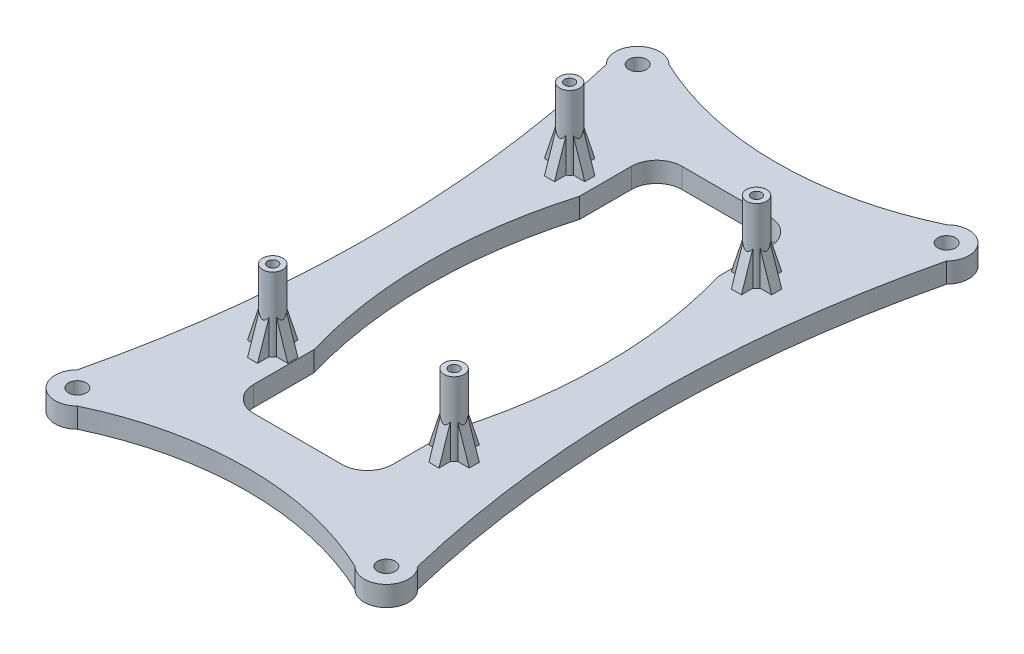
SolidWorks part; units mm, degrees
ref_plane "Front Plane" through (0, 0, 0) normal (0, 0, 1) x (1, 0, 0)
ref_plane "Top Plane" through (0, 0, 0) normal (0, 1, 0) x (1, 0, 0)
ref_plane "Right Plane" through (0, 0, 0) normal (1, 0, 0) x (0, 0, -1)
sketch "Sketch2" plane through (0, 0, 0) normal (0, 1, 0) x (1, 0, 0)
  line L0 (-8.4037, 62.6632) -> (-12.355, 66.6145) construction
  line L1 (-4.4524, 58.7119) -> (65.5476, 58.7119)
  line L2 (-4.4524, 58.7119) -> (-4.4524, -74.6281)
  line L3 (-4.4524, -74.6281) -> (65.5476, -74.6281)
  line L4 (65.5476, 58.7119) -> (65.5476, -74.6281)
  line L5 (-4.4524, 58.7119) -> (65.5476, -11.2883) construction
  line L6 (-8.4037, 62.6632) -> (-4.4524, 66.6145) construction
  line L7 (-8.4037, 62.6632) -> (-12.355, 58.7119) construction
  line L8 (30.5476, 58.7119) -> (30.5476, -74.6281) construction
  line L9 (-4.4524, -7.9581) -> (65.5476, -7.9581) construction
  line L10 (69.4989, 62.6632) -> (73.4502, 58.7119) construction
  line L11 (69.4989, 62.6632) -> (65.5476, 66.6145) construction
  line L12 (69.4989, -78.5794) -> (65.5476, -82.5307) construction
  line L13 (69.4989, -78.5794) -> (73.4502, -74.6281) construction
  line L14 (-8.4037, -78.5794) -> (-12.355, -74.6281) construction
  line L15 (-8.4037, -78.5794) -> (-4.4524, -82.5307) construction
  line L16 (-12.355, 58.7119) -> (19.3976, 26.9593)
  line L17 (19.3976, -61.9281) -> (41.6976, -61.9281)
  line L18 (13.0476, -55.5781) -> (13.0476, 39.6619)
  line L19 (19.3976, 46.0119) -> (41.6976, 46.0119)
  line L20 (48.0476, -55.5781) -> (48.0476, 39.6619)
  line L21 (13.0476, -61.9281) -> (48.0476, 46.0119) construction
  line L22 (13.0476, 46.0119) -> (48.0476, -61.9281) construction
  line L23 (19.3976, 46.0119) -> (41.6976, 46.0119)
  line L24 (19.3976, 46.0119) -> (19.3976, -61.9281)
  line L25 (19.3976, -61.9281) -> (41.6976, -61.9281)
  line L26 (41.6976, 46.0119) -> (41.6976, -61.9281)
  circle A0 centre (-8.4037, 62.6632) radius 5.588
  circle A1 centre (-8.4037, 62.6632) radius 2.2225
  circle A2 centre (69.4989, 62.6632) radius 2.2225
  circle A3 centre (69.4989, 62.6632) radius 5.588
  circle A4 centre (69.4989, -78.5794) radius 5.588
  circle A5 centre (69.4989, -78.5794) radius 2.2225
  circle A6 centre (-8.4037, -78.5794) radius 2.2225
  circle A7 centre (-8.4037, -78.5794) radius 5.588
  arc A8 (-4.4524, 66.6145) -> (65.5476, 66.6145) centre (30.5476, 140.169) ccw
  arc A9 (73.4502, 58.7119) -> (73.4502, -74.6281) centre (350.7277, -7.9581) ccw
  arc A10 (-12.355, 58.7119) -> (-12.355, -74.6281) centre (-289.6325, -7.9581) cw
  arc A11 (-4.4524, -82.5307) -> (65.5476, -82.5307) centre (30.5476, -156.0852) cw
  arc A12 (13.0476, -55.5781) -> (19.3976, -61.9281) centre (19.3976, -55.5781) ccw
  arc A13 (41.6976, -61.9281) -> (48.0476, -55.5781) centre (41.6976, -55.5781) ccw
  arc A14 (48.0476, 39.6619) -> (41.6976, 46.0119) centre (41.6976, 39.6619) ccw
  arc A15 (13.0476, 39.6619) -> (19.3976, 46.0119) centre (19.3976, 39.6619) cw
  point P13 (-4.4524, -7.9581)
  point P17 (65.5476, -7.9581)
  point P36 (30.5476, -7.9581)
  dimension "D3" = 11.176
  dimension "D4" = 4.445
  dimension "D7" = 6.35
  dimension "D1" = 133.34
  dimension "D2" = 70
  dimension "D5" = 35
  dimension "D6" = 12.7
extrude "Boss-Extrude1" add sketch "Sketch2" along normal blind 5.08 contours L4 L1 L2 L3 L18 A15 L19 A14 L20 A13 L17 A12 | A0 A10 L2 | A0 A1 | A8 A0 L1 | A8 L1 A3 | A3 A2 | A9 A3 L4 | A9 L4 A4 | L3 A11 A4 | A4 A5 | A7 A11 L3 | L2 A10 A7 | A7 A6 | A0 L16 L2 region at (5.086, 0, -60.8863) region at (13.0476, 0, -57.2059) region at (-6.5606, 0, -55.2907) region at (-8.4037, 0, -57.2333) region at (56.0092, 0, -60.8863) region at (-6.7588, 0, -39.0455) region at (67.8274, 0, -41.2329) region at (64.069, 0, -62.6632) region at (-6.7321, 0, 57.149) region at (67.8274, 0, 57.149) region at (5.086, 0, 76.8025) region at (-3.3871, 0, 76.5015) region at (56.0092, 0, 76.8025) region at (69.4989, 0, 73.1495)
sketch "Sketch3" plane through (0, 5.08, 0) normal (0, 1, 0) x (1, 0, 0)
  line L0 (30.5476, 58.7119) -> (65.5476, 58.7119) construction
  line L1 (65.5476, -7.9581) -> (65.5476, 58.7119) construction
  line L2 (-4.4524, -7.9581) -> (-4.4524, 58.7119) construction
  line L3 (-4.4524, 58.7119) -> (30.5476, 58.7119) construction
  line L4 (-4.4524, -7.9581) -> (-4.4524, -74.6281) construction
  line L5 (-4.4524, -74.6281) -> (65.5476, -74.6281) construction
  line L6 (65.5476, -74.6281) -> (65.5476, -7.9581) construction
  line L7 (7.6876, -45.4181) -> (53.4076, -45.4181) construction
  line L8 (7.9936, 31.6609) -> (7.9936, 19.9149) construction
  line L9 (5.4536, 29.1209) -> (-1.0411, 29.1209) construction
  line L10 (53.7136, 27.9779) -> (60.8959, 27.9779) construction
  arc A0 (-4.4524, 66.6145) -> (65.5476, 66.6145) centre (30.5476, 140.169) ccw construction
  arc A1 (73.4502, 58.7119) -> (73.4502, -74.6281) centre (350.7277, -7.9581) ccw construction
  arc A2 (-12.355, -74.6281) -> (-12.355, 58.7119) centre (-289.6325, -7.9581) ccw construction
  arc A3 (65.5476, -82.5307) -> (-4.4524, -82.5307) centre (30.5476, -156.0852) ccw construction
  circle A4 centre (7.6876, -45.4181) radius 2.54
  circle A5 centre (53.4076, -45.4181) radius 2.54
  circle A6 centre (5.4536, 31.6609) radius 2.54
  circle A7 centre (53.7136, 30.5179) radius 2.54
  point P10 (30.5476, -74.6281)
  dimension "D4" = 5.08
  dimension "D1" = 29.21
  dimension "D2" = 45.72
  dimension "D3" = 12.14
  dimension "D5" = 48.26
  dimension "D6" = 12.446
  dimension "D7" = 29.591
  dimension "D8" = 30.734
extrude "Boss-Extrude2" add sketch "Sketch3" along normal blind 18.542
sketch "Sketch5" plane through (0, 5.08, 0) normal (0, 1, 0) x (1, 0, 0)
  line L0 (19.3976, 46.0119) -> (41.6976, 46.0119) construction
  line L1 (0.3736, 48.5519) -> (58.7936, 48.5519)
  line L2 (0.3736, 48.5519) -> (0.3736, -64.4681)
  line L3 (0.3736, -64.4681) -> (58.7936, -64.4681)
  line L4 (58.7936, 48.5519) -> (58.7936, -64.4681)
  line L5 (0.3736, 34.4851) -> (14.4404, 48.5519)
  line L6 (19.3976, -61.9281) -> (41.6976, -61.9281) construction
  line L7 (2.9136, 31.6609) -> (2.9136, 24.292) construction
  line L8 (56.2536, 30.5179) -> (56.2536, 22.8042) construction
  line L9 (0.3736, 26.6077) -> (11.4702, -7.9581)
  line L10 (11.4702, -7.9581) -> (0.3736, -43.4858)
  line L11 (58.7936, 27.9426) -> (50.3671, -7.9581)
  line L12 (50.3671, -7.9581) -> (58.7936, -43.4858)
  line L13 (46.6181, 48.5519) -> (58.7936, 36.3764)
  line L14 (0.3736, -52.1436) -> (14.4404, -64.4681)
  line L15 (58.7936, -54.375) -> (46.6181, -64.4681)
  circle A1 centre (5.4536, 31.6609) radius 2.54 construction
  circle A2 centre (5.4536, 31.6609) radius 2.54 construction
  circle A3 centre (53.7136, 30.5179) radius 2.54 construction
  circle A4 centre (53.7136, 30.5179) radius 2.54 construction
  arc M11 (65.5476, 66.6145) -> (-4.4524, 66.6145) centre (30.5476, 140.169) cw
  arc M12 (-4.4524, 66.6145) -> (-12.355, 58.7119) centre (-8.4037, 62.6632) ccw
  arc M13 (-12.355, 58.7119) -> (-12.355, -74.6281) centre (-289.6325, -7.9581) cw
  arc M14 (-12.355, -74.6281) -> (-4.4524, -82.5307) centre (-8.4037, -78.5794) ccw
  arc M15 (-4.4524, -82.5307) -> (65.5476, -82.5307) centre (30.5476, -156.0852) cw
  arc M16 (65.5476, -82.5307) -> (73.4502, -74.6281) centre (69.4989, -78.5794) ccw
  arc M17 (73.4502, -74.6281) -> (73.4502, 58.7119) centre (350.7277, -7.9581) cw
  arc M18 (73.4502, 58.7119) -> (65.5476, 66.6145) centre (69.4989, 62.6632) ccw
  circle M27 centre (-8.4037, -78.5794) radius 2.2225
  circle M28 centre (69.4989, -78.5794) radius 2.2225
  circle M29 centre (-8.4037, 62.6632) radius 2.2225
  circle M30 centre (69.4989, 62.6632) radius 2.2225
  dimension "D1" = 2.54
  dimension "D2" = 2.54
  dimension "D3" = 2.54
  dimension "D4" = 2.54
extrude "Cut-Extrude2" [suppressed] cut sketch "Sketch5" against normal through all both and the other way through all contours L10 L9 L2 | L2 L5 L1 | L1 L13 L4 | L11 L12 L4 | L4 L15 L3 | L14 L2 L3 | L1 L4 L3 L2 M18 M11 M12 M13 M14 M15 M16 M17 M28 M30 M29 M27
sketch "Sketch6" plane through (0, 5.08, 0) normal (0, 1, 0) x (1, 0, 0)
  line L0 (7.6876, -42.8781) -> (13.0476, -42.8781) construction
  line L1 (13.0476, -55.5781) -> (13.0476, 39.6619) construction
  line L2 (5.4536, 29.1209) -> (13.0476, 29.1209) construction
  line L3 (13.0476, 26.5809) -> (13.0476, -40.3381)
  line L4 (30.5476, 46.0119) -> (30.5476, -61.9281) construction
  line L5 (19.3976, 46.0119) -> (41.6976, 46.0119) construction
  line L6 (19.3976, -61.9281) -> (41.6976, -61.9281) construction
  line L7 (48.0476, 26.5809) -> (48.0476, -40.3381)
  circle A0 centre (7.6876, -45.4181) radius 2.54 construction
  circle A1 centre (7.6876, -45.4181) radius 2.54 construction
  circle A2 centre (5.4536, 31.6609) radius 2.54 construction
  circle A3 centre (5.4536, 31.6609) radius 2.54 construction
  arc A4 (13.0476, 26.5809) -> (13.0476, -40.3381) centre (127.2662, -6.8786) ccw
  arc A5 (-12.355, -74.6281) -> (-12.355, 58.7119) centre (-289.6325, -7.9581) ccw construction
  arc A6 (48.0476, 26.5809) -> (48.0476, -40.3381) centre (-66.1709, -6.8786) cw
  point P19 (8.2476, -6.8786)
  point P23 (-4.4524, -7.9581)
  dimension "D1" = 12.7
  dimension "D2" = 2.54
  dimension "D3" = 2.54
extrude "Cut-Extrude3" cut sketch "Sketch6" against normal through all
sketch "Sketch7" plane through (0, 23.622, 0) normal (0, 1, 0) x (1, 0, 0)
  line L0 (5.4536, 34.2009) -> (5.4536, 29.1209) construction
  circle A0 centre (5.4536, 31.6609) radius 2.54 construction
sketch "Sketch9" plane through (0, 23.622, 0) normal (0, 1, 0) x (1, 0, 0)
  line L0 (7.6876, -42.8781) -> (7.6876, -47.9581) construction
  circle A0 centre (7.6876, -45.4181) radius 2.54 construction
sketch "Sketch10" plane through (0, 23.622, 0) normal (0, 1, 0) x (1, 0, 0)
  line L0 (53.4076, -42.8781) -> (53.4076, -47.9581) construction
  line L1 (53.7136, 33.0579) -> (53.7136, 27.9779) construction
  circle A0 centre (53.4076, -45.4181) radius 2.54 construction
  circle A1 centre (53.7136, 30.5179) radius 2.54 construction
ref_plane "Plane2" through (53.7136, 0, 0) normal (-1, 0, 0) x (0, 0, 1)
ref_plane "Plane3" through (7.6876, 0, 0) normal (-1, 0, 0) x (0, 0, 1)
ref_plane "Plane4" through (53.4076, 0, 0) normal (-1, 0, 0) x (0, 0, 1)
sketch "Sketch11" plane through (53.7136, 0, 0) normal (-1, 0, 0) x (0, 0, 1)
  line L0 (-30.5179, 23.622) -> (-30.5179, 5.08) construction
  line L2 (-33.0579, 23.622) -> (-27.9779, 23.622) construction
  line L3 (74.6281, 5.08) -> (-58.7119, 5.08) construction
  line L4 (-30.5179, 5.08) -> (-25.4379, 5.08)
  line L5 (-25.4379, 5.08) -> (-30.5179, 20.32)
  line L6 (-30.5179, 20.32) -> (-30.5179, 5.08)
  dimension "D1" = 15.24
  dimension "D2" = 5.08
extrude "Boss-Extrude4" add sketch "Sketch11" along normal blind 1.27 and the other way blind 1.27
sketch "Sketch12" plane through (53.4076, 0, 0) normal (-1, 0, 0) x (0, 0, 1)
  line L0 (45.4181, 23.622) -> (45.4181, 13.0582) construction
  line L1 (42.8781, 23.622) -> (47.9581, 23.622) construction
  line L2 (45.4181, 13.0582) -> (45.4181, 5.08) construction
  line L3 (74.6281, 5.08) -> (-58.7119, 5.08) construction
  line L4 (45.4181, 5.08) -> (50.4981, 5.08)
  line L5 (50.4981, 5.08) -> (45.4181, 20.32)
  line L6 (45.4181, 20.32) -> (45.4181, 5.08)
  line L7 (45.4181, 5.08) -> (45.4956, 2.4891)
  dimension "D1" = 15.24
  dimension "D2" = 5.08
extrude "Boss-Extrude5" add sketch "Sketch12" along normal blind 1.27 and the other way blind 1.27 contours L5 L6 L4 region at (53.4076, 10.16, 47.1114)
sketch "Sketch13" plane through (7.6876, 0, 0) normal (-1, 0, 0) x (0, 0, 1)
  line L0 (45.4181, 23.622) -> (45.4181, 5.08) construction
  line L1 (42.8781, 23.622) -> (47.9581, 23.622) construction
  line L2 (74.6281, 5.08) -> (-58.7119, 5.08) construction
  line L3 (45.4181, 5.08) -> (50.4981, 5.08)
  line L4 (50.4981, 5.08) -> (45.4181, 20.32)
  line L5 (45.4181, 20.32) -> (45.4181, 5.08)
  dimension "D1" = 15.24
  dimension "D2" = 5.08
extrude "Boss-Extrude6" add sketch "Sketch13" along normal blind 1.27 and the other way blind 1.27
pattern_circular "CirPattern2" count 4 over 360 about axis through (53.7136, 23.622, -30.5179) along (0, 1, 0) of "Boss-Extrude4"
pattern_circular "CirPattern3" count 4 over 360 about axis through (53.4076, 23.622, 45.4181) along (0, 1, 0) of "Boss-Extrude5"
pattern_circular "CirPattern4" count 4 over 360 about axis through (7.6876, 23.622, 45.4181) along (0, 1, 0) of "Boss-Extrude6"
ref_plane "Plane5" through (5.4536, 0, 0) normal (-1, 0, 0) x (0, 0, 1)
sketch "Sketch14" plane through (5.4536, 0, 0) normal (-1, 0, 0) x (0, 0, 1)
  line L0 (-31.6609, 23.622) -> (-31.6609, 5.08) construction
  line L1 (-34.2009, 23.622) -> (-29.1209, 23.622) construction
  line L2 (74.6281, 5.08) -> (-58.7119, 5.08) construction
  line L3 (-31.6609, 20.32) -> (-26.5809, 5.08)
  line L4 (-26.5809, 5.08) -> (-31.6609, 5.08)
  line L5 (-31.6609, 5.08) -> (-31.6609, 20.32)
  dimension "D1" = 15.24
  dimension "D2" = 5.08
extrude "Boss-Extrude7" add sketch "Sketch14" along normal blind 1.27 and the other way blind 1.27
pattern_circular "CirPattern5" count 4 over 360 about axis through (5.4536, 23.622, -31.6609) along (0, 1, 0) of "Boss-Extrude7"
sketch "Sketch4" plane through (0, 23.622, 0) normal (0, 1, 0) x (1, 0, 0)
  circle A0 centre (5.4536, 31.6609) radius 1.27
  circle A1 centre (53.7136, 30.5179) radius 1.27
  circle A2 centre (53.4076, -45.4181) radius 1.27
  circle A3 centre (7.6876, -45.4181) radius 1.27
  dimension "D1" = 2.54
extrude "Cut-Extrude1" cut sketch "Sketch4" against normal through all
sketch "Sketch15" plane through (0, 0, 0) normal (0, -1, 0) x (1, 0, 0)
  line L0 (53.7136, -33.0579) -> (53.7136, -27.9779) construction
  line L1 (5.4536, -34.2009) -> (5.4536, -29.1209) construction
  line L2 (7.6876, 42.8781) -> (7.6876, 47.9581) construction
  line L3 (53.4076, 42.8781) -> (53.4076, 47.9581) construction
  circle A0 centre (53.7136, -30.5179) radius 2.3495
  circle A1 centre (5.4536, -31.6609) radius 2.3495
  circle A2 centre (7.6876, 45.4181) radius 2.3495
  circle A3 centre (53.4076, 45.4181) radius 2.3495
  dimension "D1" = 4.699
extrude "Cut-Extrude4" cut sketch "Sketch15" against normal blind 2.54
